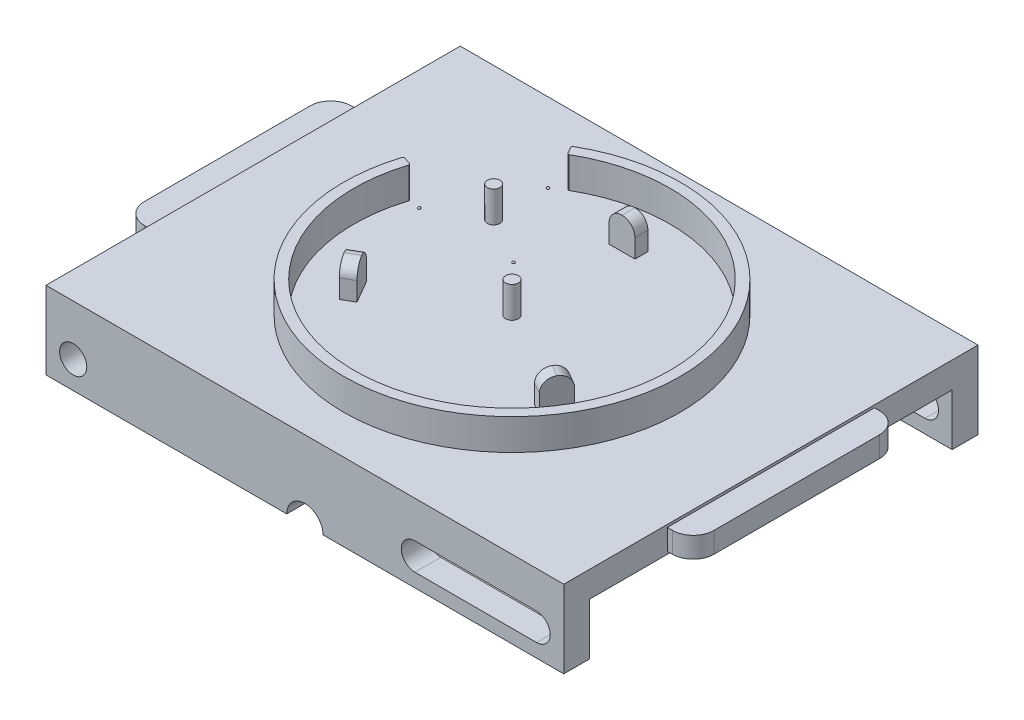
SolidWorks part; units mm, degrees
ref_plane "Vorne" through (0, 0, 0) normal (0, 0, 1) x (1, 0, 0)
ref_plane "Oben" through (0, 0, 0) normal (0, 1, 0) x (1, 0, 0)
ref_plane "Seite" through (0, 0, 0) normal (1, 0, 0) x (0, 0, -1)
sketch "Skizze1" plane through (0, 0, 0) normal (0, 1, 0) x (1, 0, 0)
  line L1 (100, -80) -> (-100, -80)
  line L2 (100, -80) -> (100, 80)
  line L3 (100, 80) -> (-100, 80)
  line L4 (-100, -80) -> (-100, 80)
  line L5 (100, -80) -> (-100, 80) construction
  line L6 (100, 80) -> (-100, -80) construction
  point P0 (0, 0)
  dimension "D1" = 160
  dimension "D2" = 200
extrude "Aufsatz-Linear austragen1" add sketch "Skizze1" along normal mid plane 10
sketch "Skizze2" plane through (0, -5, 0) normal (0, -1, 0) x (-1, 0, 0)
  line L0 (-100, 0) -> (100, 0) construction
  line L5 (100, -75) -> (-100, -75) construction
  line L6 (100, 70) -> (-100, 70)
  line L7 (100, 70) -> (100, 80)
  line L8 (100, 80) -> (-100, 80)
  line L9 (-100, 70) -> (-100, 80)
  line L10 (0, 80) -> (0, 70) construction
  line L15 (-100, -80) -> (-100, 80) construction
  line L16 (100, 80) -> (100, -80) construction
  line L17 (0, -80) -> (0, 80) construction
  line L18 (100, -80) -> (-100, -80) construction
  line L19 (-100, 80) -> (100, 80) construction
  line L20 (100, 75) -> (-100, 75) construction
  line L21 (0, -80) -> (0, -70) construction
  line L22 (-100, -70) -> (-100, -80)
  line L23 (100, -80) -> (-100, -80)
  line L24 (100, -70) -> (100, -80)
  line L25 (100, -70) -> (-100, -70)
  point P28 (0, -75)
  point P672 (0, 75)
  dimension "D1" = 200
  dimension "D2" = 10
  dimension "D3" = 80
extrude "Aufsatz-Linear austragen2" add sketch "Skizze2" along normal blind 20
sketch "Skizze3" plane through (0, 0, 0) normal (0, 0, 1) x (1, 0, 0)
  line L0 (42.5, -9.25) -> (89.5, -9.25)
  line L1 (42.5, -19.75) -> (89.5, -19.75)
  line L2 (100, -25) -> (-100, -25) construction
  line L3 (100, -25) -> (100, 5) construction
  line L4 (-100, -25) -> (-100, 5) construction
  line L5 (-7, -25) -> (7, -25)
  circle A0 centre (-89.5, -14.5) radius 5.25
  arc A1 (89.5, -19.75) -> (89.5, -9.25) centre (89.5, -14.5) ccw
  arc A2 (42.5, -9.25) -> (42.5, -19.75) centre (42.5, -14.5) ccw
  arc A3 (7, -25) -> (-7, -25) centre (0, -25) ccw
  dimension "D2" = 10.5
  dimension "D6" = 7
  dimension "D1" = 10.5
  dimension "D3" = 47
  dimension "D4" = 10.5
  dimension "D5" = 10.5
extrude "Schnitt-Linear austragen1" cut sketch "Skizze3" against normal through all both and the other way through all
sketch "Skizze4" plane through (0, 5, 0) normal (0, 1, 0) x (1, 0, 0)
  line L0 (-58.0351, 18.7863) -> (-61.8407, 20.0182)
  line L1 (-100, 80) -> (-100, -80) construction
  line L2 (-31.0675, 52.4958) -> (-33.1047, 55.9382)
  line L5 (0, 0) -> (-35.4514, 28.3612) construction
  line L6 (-35.4514, 28.3612) -> (-100, 80) construction
  circle A0 centre (0, 0) radius 2.45
  circle A3 centre (-35.4514, 28.3612) radius 2.45
  arc A4 (-61.8407, 20.0182) -> (-33.1047, 55.9382) centre (0, 0) ccw
  arc A5 (-58.0351, 18.7863) -> (-31.0675, 52.4958) centre (0, 0) ccw
  point P16 (0, 0)
  dimension "D1" = 4.9
  dimension "D7" = 4
  dimension "D3" = 46
  dimension "D5" = 61
  dimension "D2" = 45.4
extrude "Aufsatz-Linear austragen3" add sketch "Skizze4" along normal blind 12
chamfer "Fase1" distance 0.4 angle 45 4 edges at (-58.0351, 11, -18.7863) (-61.8407, 11, -20.0182) (-33.1047, 11, -55.9382) (-31.0675, 11, -52.4958)
sketch "Skizze6" plane through (0, 5, 0) normal (0, 1, 0) x (1, 0, 0)
  line L0 (0, 45) -> (-38.9711, -22.5) construction
  line L1 (-38.9711, -22.5) -> (38.9711, -22.5) construction
  line L2 (38.9711, -22.5) -> (0, 45) construction
  line L3 (0, 0) -> (-38.9711, -22.5) construction
  line L4 (0, 0) -> (38.9711, -22.5) construction
  line L5 (0, 0) -> (0, 45) construction
  line L6 (43.6362, -19.4199) -> (39.3061, -16.9199)
  line L7 (39.3061, -16.9199) -> (34.3061, -25.5801)
  line L8 (34.3061, -25.5801) -> (38.6362, -28.0801)
  line L9 (38.6362, -28.0801) -> (43.6362, -19.4199)
  line L10 (-34.3061, -25.5801) -> (-39.3061, -16.9199)
  line L11 (-39.3061, -16.9199) -> (-43.6362, -19.4199)
  line L12 (-43.6362, -19.4199) -> (-38.6362, -28.0801)
  line L13 (-38.6362, -28.0801) -> (-34.3061, -25.5801)
  line L14 (5, 42.5) -> (-5, 42.5)
  line L15 (-5, 42.5) -> (-5, 47.5)
  line L16 (-5, 47.5) -> (5, 47.5)
  line L17 (5, 47.5) -> (5, 42.5)
  line L18 (5, 47.5) -> (-5, 42.5) construction
  line L19 (-5, 47.5) -> (5, 42.5) construction
  line L20 (39.3061, -16.9199) -> (38.6362, -28.0801) construction
  line L21 (34.3061, -25.5801) -> (43.6362, -19.4199) construction
  line L22 (-38.6362, -28.0801) -> (-39.3061, -16.9199) construction
  line L23 (-43.6362, -19.4199) -> (-34.3061, -25.5801) construction
  circle A0 centre (0, 0) radius 45 construction
  point P3 (-38.9711, -22.5)
  point P4 (0, 45)
  point P5 (38.9711, -22.5)
  point P19 (0, 45)
  point P22 (38.9711, -22.5)
  point P23 (-38.9711, -22.5)
  dimension "D1" = 90
  dimension "D2" = 10
  dimension "D3" = 5
extrude "Aufsatz-Linear austragen4" add sketch "Skizze6" along normal blind 12.2 separate body
fillet "Verrundung1" radius 5 2 edges at (36.4711, 17.2, 26.8301) (41.4711, 17.2, 18.1699)
fillet "Verrundung2" radius 5 2 edges at (-36.4711, 17.2, 26.8301) (-41.4711, 17.2, 18.1699)
fillet "Verrundung3" radius 5 2 edges at (-5, 17.2, -45) (5, 17.2, -45)
sketch "Skizze7" plane through (0, 0, 0) normal (0, 1, 0) x (1, 0, 0)
  line L0 (-100, 40) -> (-110, 40)
  line L1 (-100, 80) -> (-100, -80) construction
  line L2 (-110, 40) -> (-110, -40)
  line L3 (-110, -40) -> (-100, -40)
  line L4 (100, 80) -> (-100, 80) construction
  line L5 (-100, 40) -> (-100, -40)
  line L6 (0, -50) -> (0, 50) construction
  line L7 (100, 40) -> (100, -40)
  line L8 (110, -40) -> (100, -40)
  line L9 (110, 40) -> (110, -40)
  line L10 (100, 40) -> (110, 40)
  dimension "D1" = 80
  dimension "D2" = 10
  dimension "D3" = 40
extrude "Aufsatz-Linear austragen5" add sketch "Skizze7" along normal mid plane 8
fillet "Verrundung4" radius 8 4 edges at (110, 0, 40) (110, 0, -40) (-110, 0, -40) (-110, 0, 40)
sketch "Skizze8" plane through (0, 5, 0) normal (0, 1, 0) x (1, 0, 0)
  line L0 (-35.4514, 49.3612) -> (-53.638, 17.8612) construction
  line L1 (-53.638, 17.8612) -> (-17.2649, 17.8612) construction
  line L2 (-17.2649, 17.8612) -> (-35.4514, 49.3612) construction
  circle A0 centre (-35.4514, 28.3612) radius 21 construction
  circle A1 centre (-35.4514, 49.3612) radius 0.5
  circle A2 centre (-53.638, 17.8612) radius 0.5
  circle A3 centre (-17.2649, 17.8612) radius 0.5
  point P9 (0, 0)
  dimension "D1" = 42
  dimension "D2" = 1
extrude "Aufsatz-Linear austragen6" add sketch "Skizze8" along normal blind 0.5
fillet "Verrundung5" radius 0.5 3 edges at (-53.638, 5.5, -17.3612) (-17.2649, 5.5, -17.3612) (-35.4514, 5.5, -48.8612)
